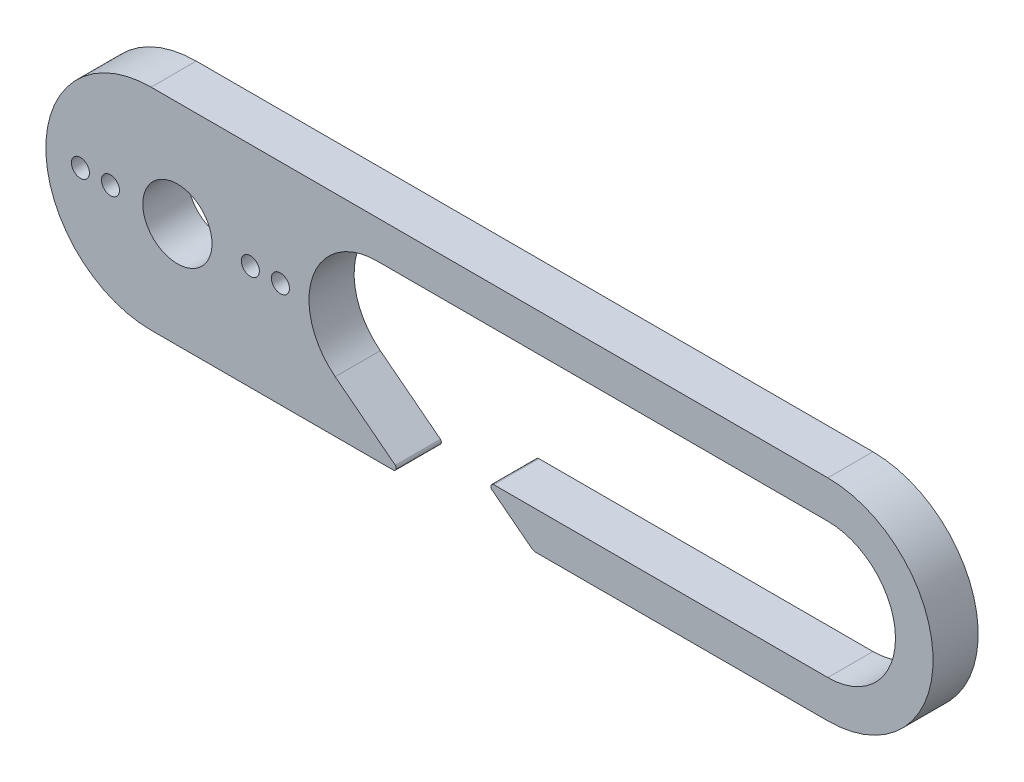
SolidWorks part; units mm, degrees
ref_plane "Front Plane" through (0, 0, 0) normal (0, 0, 1) x (1, 0, 0)
ref_plane "Top Plane" through (0, 0, 0) normal (0, 1, 0) x (1, 0, 0)
ref_plane "Right Plane" through (0, 0, 0) normal (1, 0, 0) x (0, 0, -1)
sketch "Sketch2" plane through (0, 0, 0) normal (0, 0, 1) x (1, 0, 0)
  line L0 (5.2704, 0) -> (54.3236, 0) construction
  line L1 (16.7704, 4.5) -> (46.7704, 4.5)
  line L2 (24.5608, -4.5) -> (46.7704, -4.5)
  line L3 (1.7704, 7) -> (46.7704, 7)
  line L4 (1.7704, -7) -> (17.8716, -7)
  line L5 (1.7704, 4.5) -> (46.7704, 4.5) construction
  line L6 (1.7704, -4.5) -> (46.7704, -4.5) construction
  line L7 (12.2704, 0) -> (46.7704, 0) construction
  line L8 (14.0128, -3.5561) -> (18.0106, -6.6562)
  line L10 (27.0652, -6.8951) -> (24.4383, -4.858)
  line L12 (27.3716, -7) -> (46.7704, -7)
  line L13 (1.7704, -7) -> (46.7704, -7) construction
  line L15 (12.2704, 0) -> (-5.2296, 0) construction
  arc A1 (46.7704, -4.5) -> (46.7704, 4.5) centre (46.7704, 0) ccw
  arc A2 (46.7704, -7) -> (46.7704, 7) centre (46.7704, 0) ccw
  arc A3 (1.7704, 7) -> (1.7704, -7) centre (1.7704, 0) ccw
  circle A4 centre (5.2704, 0) radius 2.5
  arc A6 (16.7704, 4.5) -> (14.0128, -3.5561) centre (16.7704, 0) ccw
  arc A7 (1.7704, 4.5) -> (1.7704, -4.5) centre (1.7704, 0) ccw construction
  arc A8 (24.4383, -4.858) -> (24.5608, -4.5) centre (24.5608, -4.7) cw
  arc A9 (27.3716, -7) -> (27.0652, -6.8951) centre (27.3716, -6.5) cw
  arc A10 (17.8716, -7) -> (18.0106, -6.6562) centre (17.8716, -6.8) ccw
  circle A11 centre (5.2704, 0) radius 2.2653 construction
  arc A12 (5.1037, 2.3451) -> (5.2704, 2.2653) centre (5.2704, 2.479) ccw
  arc A13 (5.1037, 2.3451) -> (4.7384, 2.2901) centre (4.9371, 2.2113) ccw
  arc A14 (4.6027, 2.1646) -> (4.7384, 2.2901) centre (4.5397, 2.3689) ccw
  arc A15 (5.2704, 2.2653) -> (5.437, 2.3451) centre (5.2704, 2.479) ccw
  arc A16 (5.8024, 2.2901) -> (5.437, 2.3451) centre (5.6037, 2.2113) ccw
  arc A17 (5.8024, 2.2901) -> (5.9381, 2.1646) centre (6.0011, 2.3689) ccw
  arc A18 (5.9381, 2.1646) -> (6.1209, 2.1918) centre (6.0011, 2.3689) ccw
  arc A19 (6.4537, 2.0315) -> (6.1209, 2.1918) centre (6.2406, 2.0148) ccw
  arc A20 (6.4537, 2.0315) -> (6.5464, 1.8716) centre (6.6669, 2.0483) ccw
  arc A21 (6.5464, 1.8716) -> (6.7291, 1.8438) centre (6.6669, 2.0483) ccw
  arc A22 (7, 1.5925) -> (6.7291, 1.8438) centre (6.7914, 1.6393) ccw
  arc A23 (7, 1.5925) -> (7.0414, 1.4124) centre (7.2086, 1.5456) ccw
  arc A24 (7.0414, 1.4124) -> (7.2078, 1.3319) centre (7.2086, 1.5456) ccw
  arc A25 (7.3925, 1.0119) -> (7.2078, 1.3319) centre (7.207, 1.1181) ccw
  arc A26 (7.3925, 1.0119) -> (7.379, 0.8276) centre (7.578, 0.9057) ccw
  arc A27 (7.379, 0.8276) -> (7.5143, 0.7016) centre (7.578, 0.9057) ccw
  arc A28 (7.5965, 0.3414) -> (7.5143, 0.7016) centre (7.4505, 0.4976) ccw
  arc A29 (7.5965, 0.3414) -> (7.5293, 0.1693) centre (7.7425, 0.1853) ccw
  arc A30 (7.5293, 0.1693) -> (7.6214, 0.0091) centre (7.7425, 0.1853) ccw
  arc A31 (7.5938, -0.3594) -> (7.6214, 0.0091) centre (7.5004, -0.1671) ccw
  arc A32 (7.5938, -0.3594) -> (7.4788, -0.5041) centre (7.6872, -0.5516) ccw
  arc A33 (7.4788, -0.5041) -> (7.5196, -0.6843) centre (7.6872, -0.5516) ccw
  arc A34 (7.3846, -1.0283) -> (7.5196, -0.6843) centre (7.352, -0.817) ccw
  arc A35 (7.3846, -1.0283) -> (7.2321, -1.1326) centre (7.4173, -1.2395) ccw
  arc A36 (7.2321, -1.1326) -> (7.218, -1.3169) centre (7.4173, -1.2395) ccw
  arc A37 (6.9876, -1.6058) -> (7.218, -1.3169) centre (7.0187, -1.3943) ccw
  arc A38 (6.9876, -1.6058) -> (6.8111, -1.6606) centre (6.9565, -1.8173) ccw
  arc A39 (6.8111, -1.6606) -> (6.7433, -1.8325) centre (6.9565, -1.8173) ccw
  arc A40 (6.438, -2.0406) -> (6.7433, -1.8325) centre (6.5301, -1.8477) ccw
  arc A41 (6.438, -2.0406) -> (6.2532, -2.0409) centre (6.346, -2.2335) ccw
  arc A42 (6.2532, -2.0409) -> (6.1377, -2.1852) centre (6.346, -2.2335) ccw
  arc A43 (5.7847, -2.2941) -> (6.1377, -2.1852) centre (5.9295, -2.1369) ccw
  arc A44 (5.7847, -2.2941) -> (5.608, -2.24) centre (5.6398, -2.4513) ccw
  arc A45 (5.608, -2.24) -> (5.4551, -2.3438) centre (5.6398, -2.4513) ccw
  arc A46 (5.0856, -2.3438) -> (5.4551, -2.3438) centre (5.2704, -2.2362) ccw
  arc A47 (5.0856, -2.3438) -> (4.9328, -2.24) centre (4.9009, -2.4513) ccw
  arc A48 (4.9328, -2.24) -> (4.7561, -2.2941) centre (4.9009, -2.4513) ccw
  arc A49 (4.403, -2.1852) -> (4.7561, -2.2941) centre (4.6112, -2.1369) ccw
  arc A50 (4.403, -2.1852) -> (4.2875, -2.0409) centre (4.1948, -2.2335) ccw
  arc A51 (4.2875, -2.0409) -> (4.1027, -2.0406) centre (4.1948, -2.2335) ccw
  arc A52 (3.7974, -1.8325) -> (4.1027, -2.0406) centre (4.0107, -1.8477) ccw
  arc A53 (3.7974, -1.8325) -> (3.7296, -1.6606) centre (3.5842, -1.8173) ccw
  arc A54 (3.7296, -1.6606) -> (3.5531, -1.6058) centre (3.5842, -1.8173) ccw
  arc A55 (3.3227, -1.3169) -> (3.5531, -1.6058) centre (3.522, -1.3943) ccw
  arc A56 (3.3227, -1.3169) -> (3.3086, -1.1326) centre (3.1235, -1.2395) ccw
  arc A57 (3.3086, -1.1326) -> (3.1561, -1.0283) centre (3.1235, -1.2395) ccw
  arc A58 (3.0211, -0.6843) -> (3.1561, -1.0283) centre (3.1887, -0.817) ccw
  arc A59 (3.0211, -0.6843) -> (3.0619, -0.5041) centre (2.8535, -0.5516) ccw
  arc A60 (3.0619, -0.5041) -> (2.9469, -0.3594) centre (2.8535, -0.5516) ccw
  arc A61 (2.9193, 0.0091) -> (2.9469, -0.3594) centre (3.0404, -0.1671) ccw
  arc A62 (2.9193, 0.0091) -> (3.0114, 0.1693) centre (2.7983, 0.1853) ccw
  arc A63 (3.0114, 0.1693) -> (2.9442, 0.3414) centre (2.7983, 0.1853) ccw
  arc A64 (3.0265, 0.7016) -> (2.9442, 0.3414) centre (3.0902, 0.4976) ccw
  arc A65 (3.0265, 0.7016) -> (3.1617, 0.8276) centre (2.9627, 0.9057) ccw
  arc A66 (3.1617, 0.8276) -> (3.1482, 1.0119) centre (2.9627, 0.9057) ccw
  arc A67 (3.333, 1.3319) -> (3.1482, 1.0119) centre (3.3337, 1.1181) ccw
  arc A68 (3.333, 1.3319) -> (3.4993, 1.4124) centre (3.3322, 1.5456) ccw
  arc A69 (3.4993, 1.4124) -> (3.5408, 1.5925) centre (3.3322, 1.5456) ccw
  arc A70 (3.8116, 1.8438) -> (3.5408, 1.5925) centre (3.7493, 1.6393) ccw
  arc A71 (3.8116, 1.8438) -> (3.9943, 1.8716) centre (3.8739, 2.0483) ccw
  arc A72 (3.9943, 1.8716) -> (4.087, 2.0315) centre (3.8739, 2.0483) ccw
  arc A73 (4.4199, 2.1918) -> (4.087, 2.0315) centre (4.3001, 2.0148) ccw
  arc A74 (4.4199, 2.1918) -> (4.6027, 2.1646) centre (4.5397, 2.3689) ccw
  circle A75 centre (3.5204, 0) radius 1.05
  circle A76 centre (3.5204, 0) radius 2.3
  circle A77 centre (8.3704, 0) radius 0.6
  circle A78 centre (10.3704, 0) radius 0.6
  circle A79 centre (12.3704, 0) radius 0.6
  circle A80 centre (-0.9296, 0) radius 0.6
  circle A81 centre (-2.9296, 0) radius 0.6
  circle A82 centre (-4.9296, 0) radius 0.6
  point P3 (25, 0)
  point P32 (5.2704, 0)
  point P34 (5.2704, 0)
  point P159 (5.2704, 0)
  point P176 (3.5204, 0)
  dimension "D2" = 30
  dimension "D3" = 45
  dimension "D5" = 5
  dimension "D6" = 4.5
  dimension "D7" = 4.5
  dimension "D8" = 0.2
  dimension "D9" = 0.5
  dimension "D10" = 0.2
  dimension "D1" = 2.5
  dimension "D4" = 3.5
  dimension "D11" = 9.5
  dimension "D12" = 2.2362
  dimension "D13" = 2
  dimension "D14" = 2
  dimension "D15" = 2
  dimension "D16" = 2
  dimension "D17" = 4.45
  dimension "D18" = 4.85
extrude "Boss-Extrude1" add sketch "Sketch2" along normal blind 3 contours A82 A3 L4 A10 L8 A6 A79 L1 A1 L2 A8 L10 A9 L12 A2 L3 A81 A80 A78 A77 A4 A76 | A6 A79 | A3 A82 | A77 A28 A27 A26 A25 A24 A23 A22 A21 A20 A19 A18 A17 A16 A15 A12 A13 A14 A74 A73 A76 A52 A51 A50 A49 A48 A47 A46 A45 A44 A43 A42 A41 A40 A39 A38 A37 A36 A35 A34 A33 A32 | A76 A73 A74 A14 A13 A12 A15 A16 A17 A18 A19 A20 A21 A22 A23 A24 A25 A26 A27 A28 A29 A30 A31 A32 A33 A34 A35 A36 A37 A38 A39 A40 A41 A42 A43 A44 A45 A46 A47 A48 A49 A50 A4 region at (13.4078, 3.8427, 0) region at (12.0684, 0, 0) region at (-4.8238, 0, 0) region at (6.5376, -2.0829, 0) region at (6.2544, -0.003, 0)
